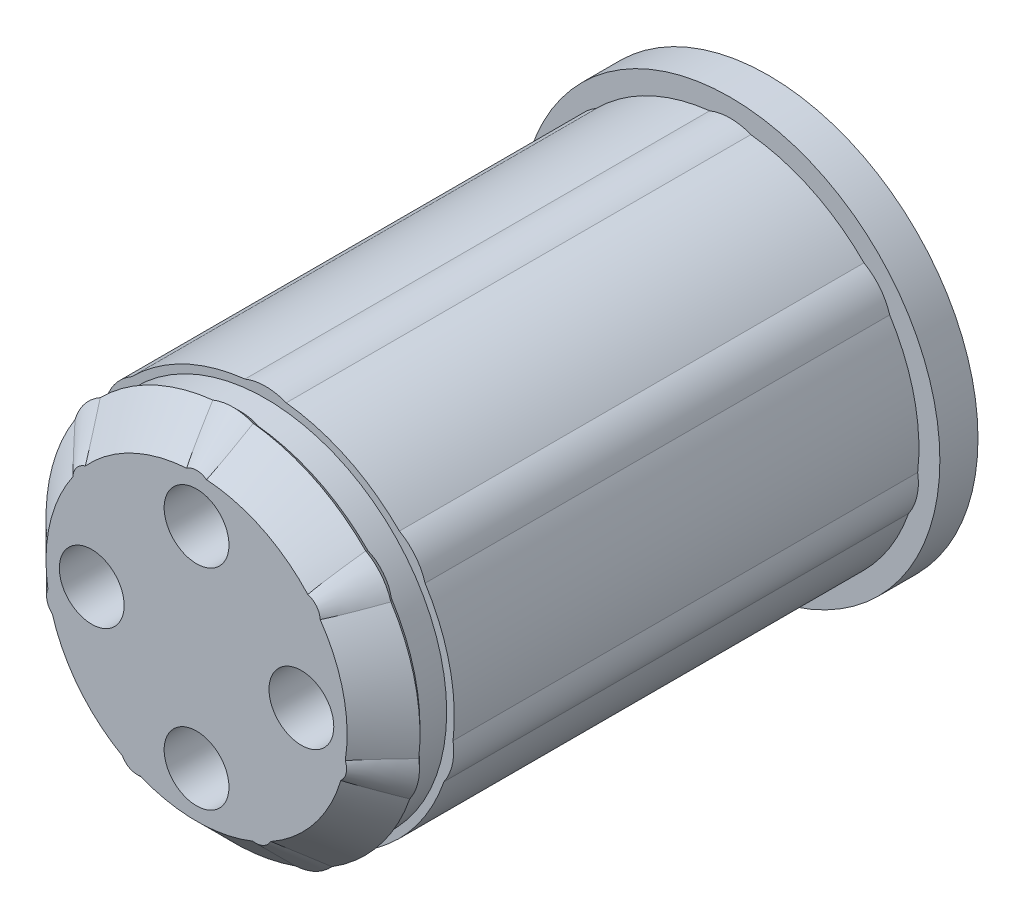
SolidWorks part; units mm, degrees
ref_plane "Ebene vorne" through (0, 0, 0) normal (0, 0, 1) x (1, 0, 0)
ref_plane "Ebene oben" through (0, 0, 0) normal (0, 1, 0) x (1, 0, 0)
ref_plane "Ebene rechts" through (0, 0, 0) normal (1, 0, 0) x (0, 0, -1)
sketch "Skizze1" plane through (0, 0, 0) normal (0, 0, 1) x (1, 0, 0)
  line L0 (0, 0) -> (0, 7.15) construction
  circle A0 centre (0, 0) radius 9.9
  circle A1 centre (0, 0) radius 10.05 construction
  circle A2 centre (0, 7.15) radius 2.9
  circle A7 centre (5.5901, 4.458) radius 2.9
  circle A8 centre (6.9707, -1.591) radius 2.9
  circle A9 centre (3.1023, -6.4419) radius 2.9
  circle A10 centre (-3.1023, -6.4419) radius 2.9
  circle A11 centre (-6.9707, -1.591) radius 2.9
  circle A12 centre (-5.5901, 4.458) radius 2.9
  point P17 (0, 0)
  point P21 (0, 0)
  dimension "D1" = 19.8
  dimension "D2" = 20.1
  dimension "D3" = 5.8
  dimension "D4" = 7
extrude "Aufsatz-Linear austragen1" add sketch "Skizze1" along normal blind 30 contours A0 A12 | A0 A2 | A0 A7 | A0 A8 | A0 A9 | A0 A10 | A0 A11 | A0 A11 | A0 A12 | A0 A2 | A0 A8 | A0 A9 | A0 A10 | A12 A0 A11 A10 A9 A8 A7 A2 | A0 A7 region at (0, 0, 0) region at (5.5718, 4.4434, 0) region at (7.7779, 6.2027, 0) region at (9.6989, -2.2137, 0) region at (6.948, -1.5858, 0) region at (0, 7.1267, 0) region at (0, 9.9483, 0) region at (4.3164, -8.9631, 0) region at (3.0921, -6.4209, 0) region at (-5.5718, 4.4434, 0) region at (-7.7779, 6.2027, 0) region at (-4.3164, -8.9631, 0) region at (-3.0921, -6.4209, 0) region at (-6.948, -1.5858, 0) region at (-9.6989, -2.2137, 0)
sketch "Skizze2" plane through (0, 0, 0) normal (0, 0, 1) x (1, 0, 0)
  circle A0 centre (0, 0) radius 11
  dimension "D1" = 22
extrude "Aufsatz-Linear austragen2" add sketch "Skizze2" along normal blind 2
chamfer "Fase1" distance 2 angle 45 14 edges at (9.798, -2.2363, 30) (7.7401, -6.1725, 30) (4.3605, -9.0547, 30) (0, -9.9, 30) (-4.3605, -9.0547, 30) (-7.7401, -6.1725, 30) (-9.798, -2.2363, 30) (-9.6518, 2.203, 30) (-7.8574, 6.2661, 30) (-4.2954, 8.9196, 30) (0, 10.05, 30) (4.2954, 8.9196, 30) (7.8574, 6.2661, 30) (9.6518, 2.203, 30)
sketch "Skizze3" plane through (0, 0, 2) normal (0, 0, 1) x (1, 0, 0)
  line L0 (0, 0) -> (0, 5.5) construction
  circle A0 centre (0, 0) radius 5.5 construction
  circle A1 centre (0, 5.5) radius 1.7
  circle A2 centre (5.5, 0) radius 1.7
  circle A3 centre (0, -5.5) radius 1.7
  circle A4 centre (-5.5, 0) radius 1.7
  point P14 (0, 0)
  dimension "D1" = 5.5
  dimension "D2" = 3.4
  dimension "D3" = 4
extrude "Schnitt-Linear austragen1" cut sketch "Skizze3" against normal through all and the other way through all
sketch "Skizze4" plane through (0, 0, 0) normal (1, 0, 0) x (0, 0, -1)
  line L0 (-2, 10.05) -> (-28, 10.05) construction
  line L1 (-27.6766, 10.05) -> (-26.3766, 10.05)
  line L2 (-27.6766, 10.05) -> (-27.6766, 9.5)
  line L3 (-27.6766, 9.5) -> (-26.3766, 9.5)
  line L4 (-26.3766, 10.05) -> (-26.3766, 9.5)
  line L6 (0, 0) -> (3.3435, 0) construction
  line L7 (-26.1766, 11.225) -> (-26.1766, -11.225) construction
  point P6 (-26.7284, 9.5)
  dimension "D1" = 0.2
  dimension "D2" = 19
  dimension "D3" = 1.3
revolve "Schnitt-Rotation1" cut sketch "Skizze4" angle 360 about L6
chamfer "Fase2" distance 0.5 angle 45 14 edges at (9.798, -2.2363, 27.6766) (7.7401, -6.1725, 27.6766) (4.3605, -9.0547, 27.6766) (0, -9.9, 27.6766) (-4.3605, -9.0547, 27.6766) (-7.7401, -6.1725, 27.6766) (-9.798, -2.2363, 27.6766) (-9.6518, 2.203, 27.6766) (-7.8574, 6.2661, 27.6766) (-4.2954, 8.9196, 27.6766) (0, 10.05, 27.6766) (9.6518, 2.203, 27.6766) (7.8574, 6.2661, 27.6766) (4.2954, 8.9196, 27.6766)
